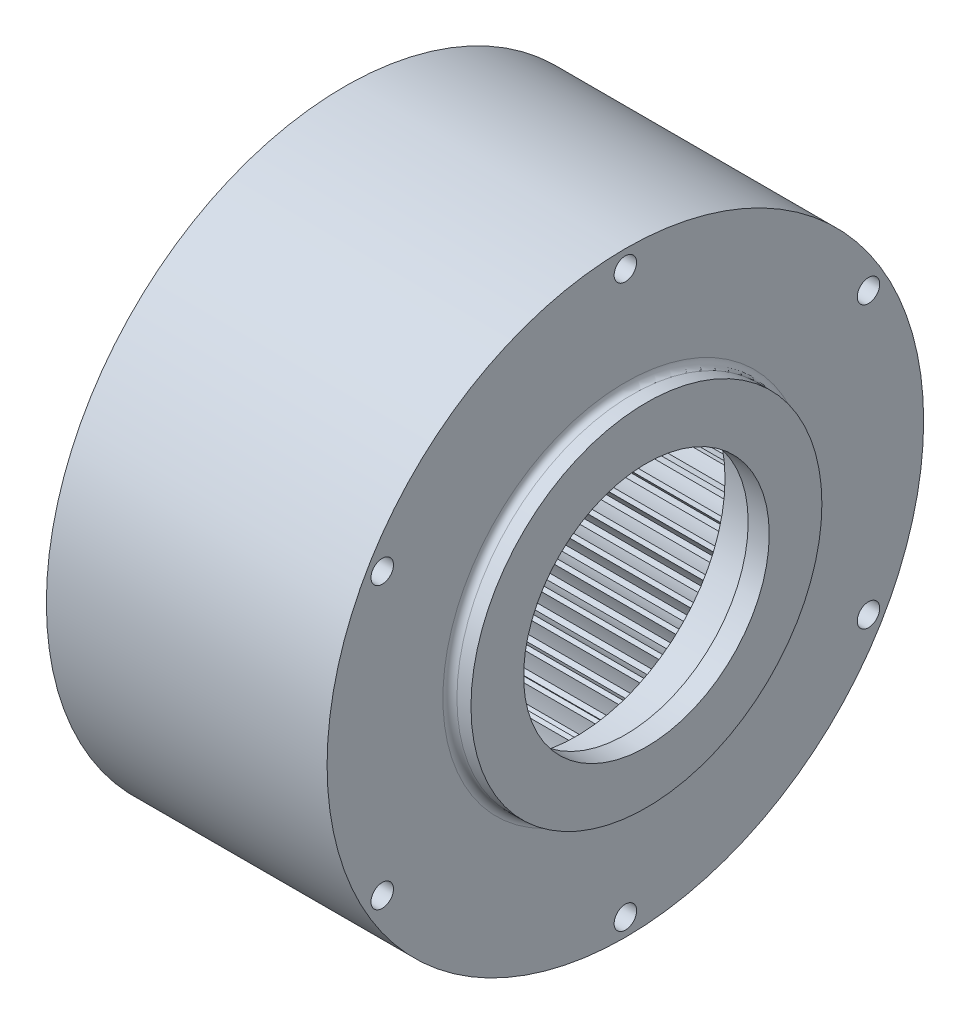
SolidWorks part; units mm, degrees
ref_plane "Plane1" through (0, 0, 0) normal (0, 0, 1) x (1, 0, 0)
ref_plane "Plane2" through (0, 0, 0) normal (0, 1, 0) x (1, 0, 0)
ref_plane "Plane3" through (0, 0, 0) normal (1, 0, 0) x (0, 0, -1)
sketch "HoldingSke" plane through (0, 0, 0) normal (0, 1, 0) x (1, 0, 0)
  line L0 (0, 0) -> (0.342, -0.9397)
  line L1 (-15, 0) -> (100, 0) construction
  line L2 (0, 0) -> (-2.1039, 2.3779)
  line L3 (0, 0) -> (-11.863, 4.5341)
  line L4 (0, 0) -> (2.9537, 8.1152)
  line L5 (0, 0) -> (-23.7986, -8.8762)
  line L6 (0, 0) -> (-10.5278, -7.1032)
  line L7 (-2.1039, 2.3779) -> (3.3635, 27.1825)
  line L8 (-76.2, 3.3779) -> (-54.61, 3.3779)
  line L9 (-71.009, 38.7566) -> (-53.1078, 45.2721)
  line L10 (-76.2, 71.12) -> (104.1128, 71.12)
  line L11 (0, 0) -> (-30, 0)
  line L12 (-76.2, 101.6) -> (-76.162, 101.6)
  line L13 (24.9733, 27.94) -> (52.9518, 28.4284)
  line L14 (24.9733, 27.94) -> (24.9743, 27.94)
  line L15 (24.9733, 27.94) -> (100.4006, 29.5858)
  circle A0 centre (0, 0) radius 42.5
  circle A1 centre (0, 0) radius 12.7
  circle A2 centre (0, 0) radius 12.7
  dimension "MHD" = 25.4
  dimension "Hub_dia" = 25.4
  dimension "Diameter" = 85
  dimension "Num_teeth" = 70
  dimension "Pitch" = 1
  dimension "Overall_len" = 25.4
  dimension "Show_teeth" = 70
  dimension "Thickness" = 12.7
  dimension "OAL" = 25.4001
  dimension "T_dim" = 21.59
  dimension "Ap" = 20
  dimension "H" = 19.05
  dimension "Pitch_radius" = 180.3128
  dimension "Width" = 30
  dimension "Backlash" = 0.038
  dimension "Addendum_fac" = 1
  dimension "Dedendum_fac" = 1.25
  dimension "Clearance_fac" = 0.25
  dimension "Dedendum_add" = 0.001
  dimension "Module" = 1
sketch "BasProSke" plane through (0, 0, 0) normal (0, 1, 0) x (1, 0, 0)
  line L0 (-10, 0) -> (60, 0) construction
  line L1 (0, 34) -> (0, 42.5)
  line L2 (0, 34) -> (30, 34)
  line L3 (30, 34) -> (30, 42.5)
  line L4 (30, 42.5) -> (0, 42.5)
  dimension "Diameter" = 85
  dimension "Thickness" = 30
  dimension "Inside_diameter" = 68
revolve "Base-Revolve" add sketch "BasProSke" angle 360 about L0
sketch "TooCutSke" plane through (0, 0, 0) normal (1, 0, 0) x (0, 0, -1)
  line L3 (0.8803, 34.9889) -> (0.8803, 53.6633) construction
  line L4 (0, 0) -> (0, 59.563) construction
  line L5 (0, 0) -> (-3.0655, 68.2587) construction
  line L6 (-15.5382, 28.9323) -> (36.4767, 31.2683) construction
  circle A0 centre (0, 0) radius 35 construction
  circle A1 centre (0, 0) radius 36.251 construction
  circle A2 centre (0, 0) radius 29.6003 construction
  circle A3 centre (0, 0) radius 33.9746 construction
  arc A4 (1.2263, 33.9525) -> (0.3588, 36.2492) centre (-15.5382, 28.9323) ccw
  arc A5 (1.2263, 33.9525) -> (-1.2263, 33.9525) centre (0, 0) ccw
  arc A6 (0.3588, 36.2492) -> (-0.3588, 36.2492) centre (0, 0) ccw
  arc A7 (-0.3588, 36.2492) -> (-1.2263, 33.9525) centre (15.5382, 28.9323) ccw
  dimension "Pitch_dia" = 70
  dimension "Base_dia" = 59.2006
  dimension "Root_dia" = 72.502
  dimension "Overcut_dia" = 67.9492
  dimension "Flank_rad" = 17.5
  dimension "Half_ang" = 2.571
  dimension "Half_CT" = 0.8803
extrude "ToothCut" cut sketch "TooCutSke" along normal through all
fillet "Breaks" [suppressed] radius 0.1
fillet "RootFillets" [suppressed] radius 0.251
pattern_circular "TeethCuts" count 70 every 5.143 about axis through (-10, 0, 0) along (1, 0, 0) of "RootFillets", "Breaks", "ToothCut"
sketch "Sketch1" plane through (30, 0, 0) normal (1, 0, 0) x (0, 0, -1)
  circle A1 centre (0, 0) radius 21.2
  circle A2 centre (0, 0) radius 42.5 construction
  circle A3 centre (0, 0) radius 42.5
extrude "Boss-Extrude1" add sketch "Sketch1" along normal blind 7
sketch "Sketch2" plane through (37, 0, 0) normal (1, 0, 0) x (0, 0, -1)
  circle A0 centre (0, 0) radius 25
  circle A1 centre (0, 0) radius 17.5
extrude "Boss-Extrude2" add sketch "Sketch2" along normal blind 3
fillet "Fillet1" radius 1 1 edges at (37, 0, -25)
sketch "Sketch4" plane through (0, 0, 0) normal (-1, 0, 0) x (0, 0, 1)
  arc A0 (-21.0165, 29.5371) -> (-21.597, 29.1154) centre (0, 0) ccw construction
  circle A1 centre (0, 0) radius 42.5
  circle A2 centre (0, 0) radius 42.5
  arc A3 (-21.597, 29.1154) -> (-20.9577, 26.7726) centre (-4.4353, 32.5399) ccw construction
  arc A4 (-20.9577, 26.7726) -> (-21.4379, 26.3897) centre (0, 0) ccw construction
  arc A5 (-21.4379, 26.3897) -> (-23.5796, 27.5343) centre (-30.7371, 11.5649) ccw construction
  arc A6 (-23.5796, 27.5343) -> (-24.1199, 27.0622) centre (0, 0) ccw construction
  arc A7 (-23.5796, 27.5343) -> (-24.1199, 27.0622) centre (0, 0) ccw construction
  arc A8 (-24.1199, 27.0622) -> (-23.2732, 24.7862) centre (-7.3343, 32.0113) ccw construction
  arc A9 (-23.2732, 24.7862) -> (-23.7171, 24.3618) centre (0, 0) ccw construction
  arc A10 (-23.7171, 24.3618) -> (-25.9528, 25.3098) centre (-31.65, 8.7631) ccw construction
  arc A11 (-25.9528, 25.3098) -> (-26.4487, 24.7912) centre (0, 0) ccw construction
  arc A12 (18.2842, -31.3021) -> (18.9002, -30.9341) centre (0, 0) ccw construction
  arc A13 (18.9002, -30.9341) -> (18.4735, -28.5435) centre (1.5006, -32.8064) ccw construction
  arc A14 (18.4735, -28.5435) -> (18.986, -28.2052) centre (0, 0) ccw construction
  arc A15 (18.986, -28.2052) -> (21.0165, -29.5371) centre (29.5767, -14.2736) ccw construction
  arc A16 (21.0165, -29.5371) -> (21.597, -29.1154) centre (0, 0) ccw construction
  arc A17 (21.0165, -29.5371) -> (21.597, -29.1154) centre (0, 0) ccw construction
  arc A18 (21.597, -29.1154) -> (20.9577, -26.7726) centre (4.4353, -32.5399) ccw construction
  arc A19 (20.9577, -26.7726) -> (21.4379, -26.3897) centre (0, 0) ccw construction
  arc A20 (21.4379, -26.3897) -> (23.5796, -27.5343) centre (30.7371, -11.5649) ccw construction
  arc A21 (23.5796, -27.5343) -> (24.1199, -27.0622) centre (0, 0) ccw construction
  arc A22 (-15.4047, 32.8151) -> (-16.0512, 32.5038) centre (0, 0) ccw construction
  arc A23 (-16.0512, 32.5038) -> (-15.8405, 30.0845) centre (1.4462, 32.8089) ccw construction
  arc A24 (-15.8405, 30.0845) -> (-16.3813, 29.7935) centre (0, 0) ccw construction
  arc A25 (-16.3813, 29.7935) -> (-18.2842, 31.3021) centre (-28.1781, 16.8674) ccw construction
  arc A26 (-18.2842, 31.3021) -> (-18.9002, 30.9341) centre (0, 0) ccw construction
  arc A27 (-18.2842, 31.3021) -> (-18.9002, 30.9341) centre (0, 0) ccw construction
  arc A28 (-18.9002, 30.9341) -> (-18.4735, 28.5435) centre (-1.5006, 32.8064) ccw construction
  arc A29 (-18.4735, 28.5435) -> (-18.986, 28.2052) centre (0, 0) ccw construction
  arc A30 (-18.986, 28.2052) -> (-21.0165, 29.5371) centre (-29.5767, 14.2736) ccw construction
  arc A31 (-21.0165, 29.5371) -> (-21.597, 29.1154) centre (0, 0) ccw construction
  arc A32 (12.4012, -34.0639) -> (13.073, -33.8117) centre (0, 0) ccw construction
  arc A33 (13.073, -33.8117) -> (13.08, -31.3833) centre (-4.3813, -32.5472) ccw construction
  arc A34 (13.08, -31.3833) -> (13.6447, -31.142) centre (0, 0) ccw construction
  arc A35 (13.6447, -31.142) -> (15.4047, -32.8151) centre (26.5527, -19.3254) ccw construction
  arc A36 (15.4047, -32.8151) -> (16.0512, -32.5038) centre (0, 0) ccw construction
  arc A37 (15.4047, -32.8151) -> (16.0512, -32.5038) centre (0, 0) ccw construction
  arc A38 (16.0512, -32.5038) -> (15.8405, -30.0845) centre (-1.4462, -32.8089) ccw construction
  arc A39 (15.8405, -30.0845) -> (16.3813, -29.7935) centre (0, 0) ccw construction
  arc A40 (16.3813, -29.7935) -> (18.2842, -31.3021) centre (28.1781, -16.8674) ccw construction
  arc A41 (18.2842, -31.3021) -> (18.9002, -30.9341) centre (0, 0) ccw construction
  arc A42 (-9.2978, 35.0384) -> (-9.9895, 34.8475) centre (0, 0) ccw construction
  arc A43 (-9.9895, 34.8475) -> (-10.2141, 32.4295) centre (7.2812, 32.0234) ccw construction
  arc A44 (-10.2141, 32.4295) -> (-10.7982, 32.2397) centre (0, 0) ccw construction
  arc A45 (-10.7982, 32.2397) -> (-12.4012, 34.0639) centre (-24.7135, 21.6277) ccw construction
  arc A46 (-12.4012, 34.0639) -> (-13.073, 33.8117) centre (0, 0) ccw construction
  arc A47 (-12.4012, 34.0639) -> (-13.073, 33.8117) centre (0, 0) ccw construction
  arc A48 (-13.073, 33.8117) -> (-13.08, 31.3833) centre (4.3813, 32.5472) ccw construction
  arc A49 (-13.08, 31.3833) -> (-13.6447, 31.142) centre (0, 0) ccw construction
  arc A50 (-13.6447, 31.142) -> (-15.4047, 32.8151) centre (-26.5527, 19.3254) ccw construction
  arc A51 (-15.4047, 32.8151) -> (-16.0512, 32.5038) centre (0, 0) ccw construction
  arc A52 (6.1195, -35.7307) -> (6.8256, -35.6026) centre (0, 0) ccw construction
  arc A53 (6.8256, -35.6026) -> (7.266, -33.2145) centre (-10.1224, -31.2418) ccw construction
  arc A54 (7.266, -33.2145) -> (7.8648, -33.0779) centre (0, 0) ccw construction
  arc A55 (7.8648, -33.0779) -> (9.2978, -35.0384) centre (22.6753, -23.756) ccw construction
  arc A56 (9.2978, -35.0384) -> (9.9895, -34.8475) centre (0, 0) ccw construction
  arc A57 (9.2978, -35.0384) -> (9.9895, -34.8475) centre (0, 0) ccw construction
  arc A58 (9.9895, -34.8475) -> (10.2141, -32.4295) centre (-7.2812, -32.0234) ccw construction
  arc A59 (10.2141, -32.4295) -> (10.7982, -32.2397) centre (0, 0) ccw construction
  arc A60 (10.7982, -32.2397) -> (12.4012, -34.0639) centre (24.7135, -21.6277) ccw construction
  arc A61 (12.4012, -34.0639) -> (13.073, -33.8117) centre (0, 0) ccw construction
  arc A62 (-2.892, 36.1355) -> (-3.6067, 36.0711) centre (0, 0) ccw construction
  arc A63 (-3.6067, 36.0711) -> (-4.2595, 33.7321) centre (12.8822, 30.2087) ccw construction
  arc A64 (-4.2595, 33.7321) -> (-4.868, 33.6497) centre (0, 0) ccw construction
  arc A65 (-4.868, 33.6497) -> (-6.1195, 35.7307) centre (-20.4545, 25.6929) ccw construction
  arc A66 (-6.1195, 35.7307) -> (-6.8256, 35.6026) centre (0, 0) ccw construction
  arc A67 (-6.1195, 35.7307) -> (-6.8256, 35.6026) centre (0, 0) ccw construction
  arc A68 (-6.8256, 35.6026) -> (-7.266, 33.2145) centre (10.1224, 31.2418) ccw construction
  arc A69 (-7.266, 33.2145) -> (-7.8648, 33.0779) centre (0, 0) ccw construction
  arc A70 (-7.8648, 33.0779) -> (-9.2978, 35.0384) centre (-22.6753, 23.756) ccw construction
  arc A71 (-9.2978, 35.0384) -> (-9.9895, 34.8475) centre (0, 0) ccw construction
  arc A72 (-0.3588, -36.2492) -> (0.3588, -36.2492) centre (0, 0) ccw construction
  arc A73 (0.3588, -36.2492) -> (1.2186, -33.9782) centre (-15.5382, -28.9323) ccw construction
  arc A74 (1.2186, -33.9782) -> (1.8321, -33.9506) centre (0, 0) ccw construction
  arc A75 (1.8321, -33.9506) -> (2.892, -36.1355) centre (18.0691, -27.423) ccw construction
  arc A76 (2.892, -36.1355) -> (3.6067, -36.0711) centre (0, 0) ccw construction
  arc A77 (2.892, -36.1355) -> (3.6067, -36.0711) centre (0, 0) ccw construction
  arc A78 (3.6067, -36.0711) -> (4.2595, -33.7321) centre (-12.8822, -30.2087) ccw construction
  arc A79 (4.2595, -33.7321) -> (4.868, -33.6497) centre (0, 0) ccw construction
  arc A80 (4.868, -33.6497) -> (6.1195, -35.7307) centre (20.4545, -25.6929) ccw construction
  arc A81 (6.1195, -35.7307) -> (6.8256, -35.6026) centre (0, 0) ccw construction
  arc A82 (3.6067, 36.0711) -> (2.892, 36.1355) centre (0, 0) ccw construction
  arc A83 (2.892, 36.1355) -> (1.8321, 33.9506) centre (18.0691, 27.423) ccw construction
  arc A84 (1.8321, 33.9506) -> (1.2186, 33.9782) centre (0, 0) ccw construction
  arc A85 (1.2186, 33.9782) -> (0.3588, 36.2492) centre (-15.5382, 28.9323) ccw construction
  arc A86 (0.3588, 36.2492) -> (-0.3588, 36.2492) centre (0, 0) ccw construction
  arc A87 (0.3588, 36.2492) -> (-0.3588, 36.2492) centre (0, 0) ccw construction
  arc A88 (-0.3588, 36.2492) -> (-1.2186, 33.9782) centre (15.5382, 28.9323) ccw construction
  arc A89 (-1.2186, 33.9782) -> (-1.8321, 33.9506) centre (0, 0) ccw construction
  arc A90 (-1.8321, 33.9506) -> (-2.892, 36.1355) centre (-18.0691, 27.423) ccw construction
  arc A91 (-2.892, 36.1355) -> (-3.6067, 36.0711) centre (0, 0) ccw construction
  arc A92 (-6.8256, -35.6026) -> (-6.1195, -35.7307) centre (0, 0) ccw construction
  arc A93 (-6.1195, -35.7307) -> (-4.868, -33.6497) centre (-20.4545, -25.6929) ccw construction
  arc A94 (-4.868, -33.6497) -> (-4.2595, -33.7321) centre (0, 0) ccw construction
  arc A95 (-4.2595, -33.7321) -> (-3.6067, -36.0711) centre (12.8822, -30.2087) ccw construction
  arc A96 (-3.6067, -36.0711) -> (-2.892, -36.1355) centre (0, 0) ccw construction
  arc A97 (-3.6067, -36.0711) -> (-2.892, -36.1355) centre (0, 0) ccw construction
  arc A98 (-2.892, -36.1355) -> (-1.8321, -33.9506) centre (-18.0691, -27.423) ccw construction
  arc A99 (-1.8321, -33.9506) -> (-1.2186, -33.9782) centre (0, 0) ccw construction
  arc A100 (-1.2186, -33.9782) -> (-0.3588, -36.2492) centre (15.5382, -28.9323) ccw construction
  arc A101 (-0.3588, -36.2492) -> (0.3588, -36.2492) centre (0, 0) ccw construction
  arc A102 (9.9895, 34.8475) -> (9.2978, 35.0384) centre (0, 0) ccw construction
  arc A103 (9.2978, 35.0384) -> (7.8648, 33.0779) centre (22.6753, 23.756) ccw construction
  arc A104 (7.8648, 33.0779) -> (7.266, 33.2145) centre (0, 0) ccw construction
  arc A105 (7.266, 33.2145) -> (6.8256, 35.6026) centre (-10.1224, 31.2418) ccw construction
  arc A106 (6.8256, 35.6026) -> (6.1195, 35.7307) centre (0, 0) ccw construction
  arc A107 (6.8256, 35.6026) -> (6.1195, 35.7307) centre (0, 0) ccw construction
  arc A108 (6.1195, 35.7307) -> (4.868, 33.6497) centre (20.4545, 25.6929) ccw construction
  arc A109 (4.868, 33.6497) -> (4.2595, 33.7321) centre (0, 0) ccw construction
  arc A110 (4.2595, 33.7321) -> (3.6067, 36.0711) centre (-12.8822, 30.2087) ccw construction
  arc A111 (3.6067, 36.0711) -> (2.892, 36.1355) centre (0, 0) ccw construction
  arc A112 (-13.073, -33.8117) -> (-12.4012, -34.0639) centre (0, 0) ccw construction
  arc A113 (-12.4012, -34.0639) -> (-10.7982, -32.2397) centre (-24.7135, -21.6277) ccw construction
  arc A114 (-10.7982, -32.2397) -> (-10.2141, -32.4295) centre (0, 0) ccw construction
  arc A115 (-10.2141, -32.4295) -> (-9.9895, -34.8475) centre (7.2812, -32.0234) ccw construction
  arc A116 (-9.9895, -34.8475) -> (-9.2978, -35.0384) centre (0, 0) ccw construction
  arc A117 (-9.9895, -34.8475) -> (-9.2978, -35.0384) centre (0, 0) ccw construction
  arc A118 (-9.2978, -35.0384) -> (-7.8648, -33.0779) centre (-22.6753, -23.756) ccw construction
  arc A119 (-7.8648, -33.0779) -> (-7.266, -33.2145) centre (0, 0) ccw construction
  arc A120 (-7.266, -33.2145) -> (-6.8256, -35.6026) centre (10.1224, -31.2418) ccw construction
  arc A121 (-6.8256, -35.6026) -> (-6.1195, -35.7307) centre (0, 0) ccw construction
  arc A122 (16.0512, 32.5038) -> (15.4047, 32.8151) centre (0, 0) ccw construction
  arc A123 (15.4047, 32.8151) -> (13.6447, 31.142) centre (26.5527, 19.3254) ccw construction
  arc A124 (13.6447, 31.142) -> (13.08, 31.3833) centre (0, 0) ccw construction
  arc A125 (13.08, 31.3833) -> (13.073, 33.8117) centre (-4.3813, 32.5472) ccw construction
  arc A126 (13.073, 33.8117) -> (12.4012, 34.0639) centre (0, 0) ccw construction
  arc A127 (13.073, 33.8117) -> (12.4012, 34.0639) centre (0, 0) ccw construction
  arc A128 (12.4012, 34.0639) -> (10.7982, 32.2397) centre (24.7135, 21.6277) ccw construction
  arc A129 (10.7982, 32.2397) -> (10.2141, 32.4295) centre (0, 0) ccw construction
  arc A130 (10.2141, 32.4295) -> (9.9895, 34.8475) centre (-7.2812, 32.0234) ccw construction
  arc A131 (9.9895, 34.8475) -> (9.2978, 35.0384) centre (0, 0) ccw construction
  arc A132 (-18.9002, -30.9341) -> (-18.2842, -31.3021) centre (0, 0) ccw construction
  arc A133 (-18.2842, -31.3021) -> (-16.3813, -29.7935) centre (-28.1781, -16.8674) ccw construction
  arc A134 (-16.3813, -29.7935) -> (-15.8405, -30.0845) centre (0, 0) ccw construction
  arc A135 (-15.8405, -30.0845) -> (-16.0512, -32.5038) centre (1.4462, -32.8089) ccw construction
  arc A136 (-16.0512, -32.5038) -> (-15.4047, -32.8151) centre (0, 0) ccw construction
  arc A137 (-16.0512, -32.5038) -> (-15.4047, -32.8151) centre (0, 0) ccw construction
  arc A138 (-15.4047, -32.8151) -> (-13.6447, -31.142) centre (-26.5527, -19.3254) ccw construction
  arc A139 (-13.6447, -31.142) -> (-13.08, -31.3833) centre (0, 0) ccw construction
  arc A140 (-13.08, -31.3833) -> (-13.073, -33.8117) centre (4.3813, -32.5472) ccw construction
  arc A141 (-13.073, -33.8117) -> (-12.4012, -34.0639) centre (0, 0) ccw construction
  arc A142 (21.597, 29.1154) -> (21.0165, 29.5371) centre (0, 0) ccw construction
  arc A143 (21.0165, 29.5371) -> (18.986, 28.2052) centre (29.5767, 14.2736) ccw construction
  arc A144 (18.986, 28.2052) -> (18.4735, 28.5435) centre (0, 0) ccw construction
  arc A145 (18.4735, 28.5435) -> (18.9002, 30.9341) centre (1.5006, 32.8064) ccw construction
  arc A146 (18.9002, 30.9341) -> (18.2842, 31.3021) centre (0, 0) ccw construction
  arc A147 (18.9002, 30.9341) -> (18.2842, 31.3021) centre (0, 0) ccw construction
  arc A148 (18.2842, 31.3021) -> (16.3813, 29.7935) centre (28.1781, 16.8674) ccw construction
  arc A149 (16.3813, 29.7935) -> (15.8405, 30.0845) centre (0, 0) ccw construction
  arc A150 (15.8405, 30.0845) -> (16.0512, 32.5038) centre (-1.4462, 32.8089) ccw construction
  arc A151 (16.0512, 32.5038) -> (15.4047, 32.8151) centre (0, 0) ccw construction
  arc A152 (-24.1199, -27.0622) -> (-23.5796, -27.5343) centre (0, 0) ccw construction
  arc A153 (-23.5796, -27.5343) -> (-21.4379, -26.3897) centre (-30.7371, -11.5649) ccw construction
  arc A154 (-21.4379, -26.3897) -> (-20.9577, -26.7726) centre (0, 0) ccw construction
  arc A155 (-20.9577, -26.7726) -> (-21.597, -29.1154) centre (-4.4353, -32.5399) ccw construction
  arc A156 (-21.597, -29.1154) -> (-21.0165, -29.5371) centre (0, 0) ccw construction
  arc A157 (-21.597, -29.1154) -> (-21.0165, -29.5371) centre (0, 0) ccw construction
  arc A158 (-21.0165, -29.5371) -> (-18.986, -28.2052) centre (-29.5767, -14.2736) ccw construction
  arc A159 (-18.986, -28.2052) -> (-18.4735, -28.5435) centre (0, 0) ccw construction
  arc A160 (-18.4735, -28.5435) -> (-18.9002, -30.9341) centre (-1.5006, -32.8064) ccw construction
  arc A161 (-18.9002, -30.9341) -> (-18.2842, -31.3021) centre (0, 0) ccw construction
  arc A162 (26.4487, 24.7912) -> (25.9528, 25.3098) centre (0, 0) ccw construction
  arc A163 (25.9528, 25.3098) -> (23.7171, 24.3618) centre (31.65, 8.7631) ccw construction
  arc A164 (23.7171, 24.3618) -> (23.2732, 24.7862) centre (0, 0) ccw construction
  arc A165 (23.2732, 24.7862) -> (24.1199, 27.0622) centre (7.3343, 32.0113) ccw construction
  arc A166 (24.1199, 27.0622) -> (23.5796, 27.5343) centre (0, 0) ccw construction
  arc A167 (24.1199, 27.0622) -> (23.5796, 27.5343) centre (0, 0) ccw construction
  arc A168 (23.5796, 27.5343) -> (21.4379, 26.3897) centre (30.7371, 11.5649) ccw construction
  arc A169 (21.4379, 26.3897) -> (20.9577, 26.7726) centre (0, 0) ccw construction
  arc A170 (20.9577, 26.7726) -> (21.597, 29.1154) centre (4.4353, 32.5399) ccw construction
  arc A171 (21.597, 29.1154) -> (21.0165, 29.5371) centre (0, 0) ccw construction
  arc A172 (-28.5645, -22.3205) -> (-28.1171, -22.8815) centre (0, 0) ccw construction
  arc A173 (-28.1171, -22.8815) -> (-25.8054, -22.1378) centre (-32.3081, -5.8908) ccw construction
  arc A174 (-25.8054, -22.1378) -> (-25.4014, -22.6002) centre (0, 0) ccw construction
  arc A175 (-25.4014, -22.6002) -> (-26.4487, -24.7912) centre (-10.1743, -31.225) ccw construction
  arc A176 (-26.4487, -24.7912) -> (-25.9528, -25.3098) centre (0, 0) ccw construction
  arc A177 (-26.4487, -24.7912) -> (-25.9528, -25.3098) centre (0, 0) ccw construction
  arc A178 (-25.9528, -25.3098) -> (-23.7171, -24.3618) centre (-31.65, -8.7631) ccw construction
  arc A179 (-23.7171, -24.3618) -> (-23.2732, -24.7862) centre (0, 0) ccw construction
  arc A180 (-23.2732, -24.7862) -> (-24.1199, -27.0622) centre (-7.3343, -32.0113) ccw construction
  arc A181 (-24.1199, -27.0622) -> (-23.5796, -27.5343) centre (0, 0) ccw construction
  arc A182 (30.4503, 19.6702) -> (30.055, 20.269) centre (0, 0) ccw construction
  arc A183 (30.055, 20.269) -> (27.6859, 19.7355) centre (32.7061, 2.971) ccw construction
  arc A184 (27.6859, 19.7355) -> (27.325, 20.2323) centre (0, 0) ccw construction
  arc A185 (27.325, 20.2323) -> (28.5645, 22.3205) centre (12.9323, 30.1873) ccw construction
  arc A186 (28.5645, 22.3205) -> (28.1171, 22.8815) centre (0, 0) ccw construction
  arc A187 (28.5645, 22.3205) -> (28.1171, 22.8815) centre (0, 0) ccw construction
  arc A188 (28.1171, 22.8815) -> (25.8054, 22.1378) centre (32.3081, 5.8908) ccw construction
  arc A189 (25.8054, 22.1378) -> (25.4014, 22.6002) centre (0, 0) ccw construction
  arc A190 (25.4014, 22.6002) -> (26.4487, 24.7912) centre (10.1743, 31.225) ccw construction
  arc A191 (26.4487, 24.7912) -> (25.9528, 25.3098) centre (0, 0) ccw construction
  arc A192 (-32.0909, -16.8614) -> (-31.7509, -17.4933) centre (0, 0) ccw construction
  arc A193 (-31.7509, -17.4933) -> (-29.3436, -17.1743) centre (-32.8407, -0.0273) ccw construction
  arc A194 (-29.3436, -17.1743) -> (-29.0286, -17.7015) centre (0, 0) ccw construction
  arc A195 (-29.0286, -17.7015) -> (-30.4503, -19.6702) centre (-15.5862, -28.9065) ccw construction
  arc A196 (-30.4503, -19.6702) -> (-30.055, -20.269) centre (0, 0) ccw construction
  arc A197 (-30.4503, -19.6702) -> (-30.055, -20.269) centre (0, 0) ccw construction
  arc A198 (-30.055, -20.269) -> (-27.6859, -19.7355) centre (-32.7061, -2.971) ccw construction
  arc A199 (-27.6859, -19.7355) -> (-27.325, -20.2323) centre (0, 0) ccw construction
  arc A200 (-27.325, -20.2323) -> (-28.5645, -22.3205) centre (-12.9323, -30.1873) ccw construction
  arc A201 (-28.5645, -22.3205) -> (-28.1171, -22.8815) centre (0, 0) ccw construction
  arc A202 (33.4732, 13.917) -> (33.1912, 14.5768) centre (0, 0) ccw construction
  arc A203 (33.1912, 14.5768) -> (30.7649, 14.4748) centre (32.711, -2.9167) ccw construction
  arc A204 (30.7649, 14.4748) -> (30.4985, 15.0281) centre (0, 0) ccw construction
  arc A205 (30.4985, 15.0281) -> (32.0909, 16.8614) centre (18.1146, 27.393) ccw construction
  arc A206 (32.0909, 16.8614) -> (31.7509, 17.4933) centre (0, 0) ccw construction
  arc A207 (32.0909, 16.8614) -> (31.7509, 17.4933) centre (0, 0) ccw construction
  arc A208 (31.7509, 17.4933) -> (29.3436, 17.1743) centre (32.8407, 0.0273) ccw construction
  arc A209 (29.3436, 17.1743) -> (29.0286, 17.7015) centre (0, 0) ccw construction
  arc A210 (29.0286, 17.7015) -> (30.4503, 19.6702) centre (15.5862, 28.9065) ccw construction
  arc A211 (30.4503, 19.6702) -> (30.055, 20.269) centre (0, 0) ccw construction
  arc A212 (-34.5859, -10.8604) -> (-34.3642, -11.5428) centre (0, 0) ccw construction
  arc A213 (-34.3642, -11.5428) -> (-31.9386, -11.6588) centre (-32.3178, 5.8371) ccw construction
  arc A214 (-31.9386, -11.6588) -> (-31.7228, -12.2337) centre (0, 0) ccw construction
  arc A215 (-31.7228, -12.2337) -> (-33.4732, -13.917) centre (-20.4972, -25.6589) ccw construction
  arc A216 (-33.4732, -13.917) -> (-33.1912, -14.5768) centre (0, 0) ccw construction
  arc A217 (-33.4732, -13.917) -> (-33.1912, -14.5768) centre (0, 0) ccw construction
  arc A218 (-33.1912, -14.5768) -> (-30.7649, -14.4748) centre (-32.711, 2.9167) ccw construction
  arc A219 (-30.7649, -14.4748) -> (-30.4985, -15.0281) centre (0, 0) ccw construction
  arc A220 (-30.4985, -15.0281) -> (-32.0909, -16.8614) centre (-18.1146, -27.393) ccw construction
  arc A221 (-32.0909, -16.8614) -> (-31.7509, -17.4933) centre (0, 0) ccw construction
  arc A222 (35.4202, 7.7164) -> (35.2605, 8.416) centre (0, 0) ccw construction
  arc A223 (35.2605, 8.416) -> (32.8551, 8.7489) centre (31.6645, -8.7106) ccw construction
  arc A224 (32.8551, 8.7489) -> (32.6917, 9.3409) centre (0, 0) ccw construction
  arc A225 (32.6917, 9.3409) -> (34.5859, 10.8604) centre (22.7147, 23.7183) ccw construction
  arc A226 (34.5859, 10.8604) -> (34.3642, 11.5428) centre (0, 0) ccw construction
  arc A227 (34.5859, 10.8604) -> (34.3642, 11.5428) centre (0, 0) ccw construction
  arc A228 (34.3642, 11.5428) -> (31.9386, 11.6588) centre (32.3178, -5.8371) ccw construction
  arc A229 (31.9386, 11.6588) -> (31.7228, 12.2337) centre (0, 0) ccw construction
  arc A230 (31.7228, 12.2337) -> (33.4732, 13.917) centre (20.4972, 25.6589) ccw construction
  arc A231 (33.4732, 13.917) -> (33.1912, 14.5768) centre (0, 0) ccw construction
  arc A232 (-35.9693, -4.5103) -> (-35.873, -5.2214) centre (0, 0) ccw construction
  arc A233 (-35.873, -5.2214) -> (-33.5071, -5.7686) centre (-30.7562, 11.5139) ccw construction
  arc A234 (-33.5071, -5.7686) -> (-33.3974, -6.3728) centre (0, 0) ccw construction
  arc A235 (-33.3974, -6.3728) -> (-35.4202, -7.7164) centre (-24.7494, -21.5867) ccw construction
  arc A236 (-35.4202, -7.7164) -> (-35.2605, -8.416) centre (0, 0) ccw construction
  arc A237 (-35.4202, -7.7164) -> (-35.2605, -8.416) centre (0, 0) ccw construction
  arc A238 (-35.2605, -8.416) -> (-32.8551, -8.7489) centre (-31.6645, 8.7106) ccw construction
  arc A239 (-32.8551, -8.7489) -> (-32.6917, -9.3409) centre (0, 0) ccw construction
  arc A240 (-32.6917, -9.3409) -> (-34.5859, -10.8604) centre (-22.7147, -23.7183) ccw construction
  arc A241 (-34.5859, -10.8604) -> (-34.3642, -11.5428) centre (0, 0) ccw construction
  arc A242 (36.2288, 1.2679) -> (36.1966, 1.9847) centre (0, 0) ccw construction
  arc A243 (36.1966, 1.9847) -> (33.8893, 2.7418) centre (29.6003, -14.2245) ccw construction
  arc A244 (33.8893, 2.7418) -> (33.8342, 3.3534) centre (0, 0) ccw construction
  arc A245 (33.8342, 3.3534) -> (35.9693, 4.5103) centre (26.5847, 19.2812) ccw construction
  arc A246 (35.9693, 4.5103) -> (35.873, 5.2214) centre (0, 0) ccw construction
  arc A247 (35.9693, 4.5103) -> (35.873, 5.2214) centre (0, 0) ccw construction
  arc A248 (35.873, 5.2214) -> (33.5071, 5.7686) centre (30.7562, -11.5139) ccw construction
  arc A249 (33.5071, 5.7686) -> (33.3974, 6.3728) centre (0, 0) ccw construction
  arc A250 (33.3974, 6.3728) -> (35.4202, 7.7164) centre (24.7494, 21.5867) ccw construction
  arc A251 (35.4202, 7.7164) -> (35.2605, 8.416) centre (0, 0) ccw construction
  arc A252 (-36.1966, 1.9847) -> (-36.2288, 1.2679) centre (0, 0) ccw construction
  arc A253 (-36.2288, 1.2679) -> (-33.9986, 0.3071) centre (-28.2061, 16.8206) ccw construction
  arc A254 (-33.9986, 0.3071) -> (-33.9986, -0.3071) centre (0, 0) ccw construction
  arc A255 (-33.9986, -0.3071) -> (-36.2288, -1.2679) centre (-28.2061, -16.8206) ccw construction
  arc A256 (-36.2288, -1.2679) -> (-36.1966, -1.9847) centre (0, 0) ccw construction
  arc A257 (-36.2288, -1.2679) -> (-36.1966, -1.9847) centre (0, 0) ccw construction
  arc A258 (-36.1966, -1.9847) -> (-33.8893, -2.7418) centre (-29.6003, 14.2245) ccw construction
  arc A259 (-33.8893, -2.7418) -> (-33.8342, -3.3534) centre (0, 0) ccw construction
  arc A260 (-33.8342, -3.3534) -> (-35.9693, -4.5103) centre (-26.5847, -19.2812) ccw construction
  arc A261 (-35.9693, -4.5103) -> (-35.873, -5.2214) centre (0, 0) ccw construction
  arc A262 (35.873, -5.2214) -> (35.9693, -4.5103) centre (0, 0) ccw construction
  arc A263 (35.9693, -4.5103) -> (33.8342, -3.3534) centre (26.5847, -19.2812) ccw construction
  arc A264 (33.8342, -3.3534) -> (33.8893, -2.7418) centre (0, 0) ccw construction
  arc A265 (33.8893, -2.7418) -> (36.1966, -1.9847) centre (29.6003, 14.2245) ccw construction
  arc A266 (36.1966, -1.9847) -> (36.2288, -1.2679) centre (0, 0) ccw construction
  arc A267 (36.1966, -1.9847) -> (36.2288, -1.2679) centre (0, 0) ccw construction
  arc A268 (36.2288, -1.2679) -> (33.9986, -0.3071) centre (28.2061, -16.8206) ccw construction
  arc A269 (33.9986, -0.3071) -> (33.9986, 0.3071) centre (0, 0) ccw construction
  arc A270 (33.9986, 0.3071) -> (36.2288, 1.2679) centre (28.2061, 16.8206) ccw construction
  arc A271 (36.2288, 1.2679) -> (36.1966, 1.9847) centre (0, 0) ccw construction
  arc A272 (-35.2605, 8.416) -> (-35.4202, 7.7164) centre (0, 0) ccw construction
  arc A273 (-35.4202, 7.7164) -> (-33.3974, 6.3728) centre (-24.7494, 21.5867) ccw construction
  arc A274 (-33.3974, 6.3728) -> (-33.5071, 5.7686) centre (0, 0) ccw construction
  arc A275 (-33.5071, 5.7686) -> (-35.873, 5.2214) centre (-30.7562, -11.5139) ccw construction
  arc A276 (-35.873, 5.2214) -> (-35.9693, 4.5103) centre (0, 0) ccw construction
  arc A277 (-35.873, 5.2214) -> (-35.9693, 4.5103) centre (0, 0) ccw construction
  arc A278 (-35.9693, 4.5103) -> (-33.8342, 3.3534) centre (-26.5847, 19.2812) ccw construction
  arc A279 (-33.8342, 3.3534) -> (-33.8893, 2.7418) centre (0, 0) ccw construction
  arc A280 (-33.8893, 2.7418) -> (-36.1966, 1.9847) centre (-29.6003, -14.2245) ccw construction
  arc A281 (-36.1966, 1.9847) -> (-36.2288, 1.2679) centre (0, 0) ccw construction
  arc A282 (34.3642, -11.5428) -> (34.5859, -10.8604) centre (0, 0) ccw construction
  arc A283 (34.5859, -10.8604) -> (32.6917, -9.3409) centre (22.7147, -23.7183) ccw construction
  arc A284 (32.6917, -9.3409) -> (32.8551, -8.7489) centre (0, 0) ccw construction
  arc A285 (32.8551, -8.7489) -> (35.2605, -8.416) centre (31.6645, 8.7106) ccw construction
  arc A286 (35.2605, -8.416) -> (35.4202, -7.7164) centre (0, 0) ccw construction
  arc A287 (35.2605, -8.416) -> (35.4202, -7.7164) centre (0, 0) ccw construction
  arc A288 (35.4202, -7.7164) -> (33.3974, -6.3728) centre (24.7494, -21.5867) ccw construction
  arc A289 (33.3974, -6.3728) -> (33.5071, -5.7686) centre (0, 0) ccw construction
  arc A290 (33.5071, -5.7686) -> (35.873, -5.2214) centre (30.7562, 11.5139) ccw construction
  arc A291 (35.873, -5.2214) -> (35.9693, -4.5103) centre (0, 0) ccw construction
  arc A292 (-33.1912, 14.5768) -> (-33.4732, 13.917) centre (0, 0) ccw construction
  arc A293 (-33.4732, 13.917) -> (-31.7228, 12.2337) centre (-20.4972, 25.6589) ccw construction
  arc A294 (-31.7228, 12.2337) -> (-31.9386, 11.6588) centre (0, 0) ccw construction
  arc A295 (-31.9386, 11.6588) -> (-34.3642, 11.5428) centre (-32.3178, -5.8371) ccw construction
  arc A296 (-34.3642, 11.5428) -> (-34.5859, 10.8604) centre (0, 0) ccw construction
  arc A297 (-34.3642, 11.5428) -> (-34.5859, 10.8604) centre (0, 0) ccw construction
  arc A298 (-34.5859, 10.8604) -> (-32.6917, 9.3409) centre (-22.7147, 23.7183) ccw construction
  arc A299 (-32.6917, 9.3409) -> (-32.8551, 8.7489) centre (0, 0) ccw construction
  arc A300 (-32.8551, 8.7489) -> (-35.2605, 8.416) centre (-31.6645, -8.7106) ccw construction
  arc A301 (-35.2605, 8.416) -> (-35.4202, 7.7164) centre (0, 0) ccw construction
  arc A302 (31.7509, -17.4933) -> (32.0909, -16.8614) centre (0, 0) ccw construction
  arc A303 (32.0909, -16.8614) -> (30.4985, -15.0281) centre (18.1146, -27.393) ccw construction
  arc A304 (30.4985, -15.0281) -> (30.7649, -14.4748) centre (0, 0) ccw construction
  arc A305 (30.7649, -14.4748) -> (33.1912, -14.5768) centre (32.711, 2.9167) ccw construction
  arc A306 (33.1912, -14.5768) -> (33.4732, -13.917) centre (0, 0) ccw construction
  arc A307 (33.1912, -14.5768) -> (33.4732, -13.917) centre (0, 0) ccw construction
  arc A308 (33.4732, -13.917) -> (31.7228, -12.2337) centre (20.4972, -25.6589) ccw construction
  arc A309 (31.7228, -12.2337) -> (31.9386, -11.6588) centre (0, 0) ccw construction
  arc A310 (31.9386, -11.6588) -> (34.3642, -11.5428) centre (32.3178, 5.8371) ccw construction
  arc A311 (34.3642, -11.5428) -> (34.5859, -10.8604) centre (0, 0) ccw construction
  arc A312 (-30.055, 20.269) -> (-30.4503, 19.6702) centre (0, 0) ccw construction
  arc A313 (-30.4503, 19.6702) -> (-29.0286, 17.7015) centre (-15.5862, 28.9065) ccw construction
  arc A314 (-29.0286, 17.7015) -> (-29.3436, 17.1743) centre (0, 0) ccw construction
  arc A315 (-29.3436, 17.1743) -> (-31.7509, 17.4933) centre (-32.8407, 0.0273) ccw construction
  arc A316 (-31.7509, 17.4933) -> (-32.0909, 16.8614) centre (0, 0) ccw construction
  arc A317 (-31.7509, 17.4933) -> (-32.0909, 16.8614) centre (0, 0) ccw construction
  arc A318 (-32.0909, 16.8614) -> (-30.4985, 15.0281) centre (-18.1146, 27.393) ccw construction
  arc A319 (-30.4985, 15.0281) -> (-30.7649, 14.4748) centre (0, 0) ccw construction
  arc A320 (-30.7649, 14.4748) -> (-33.1912, 14.5768) centre (-32.711, -2.9167) ccw construction
  arc A321 (-33.1912, 14.5768) -> (-33.4732, 13.917) centre (0, 0) ccw construction
  arc A322 (28.1171, -22.8815) -> (28.5645, -22.3205) centre (0, 0) ccw construction
  arc A323 (28.5645, -22.3205) -> (27.325, -20.2323) centre (12.9323, -30.1873) ccw construction
  arc A324 (27.325, -20.2323) -> (27.6859, -19.7355) centre (0, 0) ccw construction
  arc A325 (27.6859, -19.7355) -> (30.055, -20.269) centre (32.7061, -2.971) ccw construction
  arc A326 (30.055, -20.269) -> (30.4503, -19.6702) centre (0, 0) ccw construction
  arc A327 (30.055, -20.269) -> (30.4503, -19.6702) centre (0, 0) ccw construction
  arc A328 (30.4503, -19.6702) -> (29.0286, -17.7015) centre (15.5862, -28.9065) ccw construction
  arc A329 (29.0286, -17.7015) -> (29.3436, -17.1743) centre (0, 0) ccw construction
  arc A330 (29.3436, -17.1743) -> (31.7509, -17.4933) centre (32.8407, -0.0273) ccw construction
  arc A331 (31.7509, -17.4933) -> (32.0909, -16.8614) centre (0, 0) ccw construction
  arc A332 (-25.9528, 25.3098) -> (-26.4487, 24.7912) centre (0, 0) ccw construction
  arc A333 (-26.4487, 24.7912) -> (-25.4014, 22.6002) centre (-10.1743, 31.225) ccw construction
  arc A334 (-25.4014, 22.6002) -> (-25.8054, 22.1378) centre (0, 0) ccw construction
  arc A335 (-25.8054, 22.1378) -> (-28.1171, 22.8815) centre (-32.3081, 5.8908) ccw construction
  arc A336 (-28.1171, 22.8815) -> (-28.5645, 22.3205) centre (0, 0) ccw construction
  arc A337 (-28.1171, 22.8815) -> (-28.5645, 22.3205) centre (0, 0) ccw construction
  arc A338 (-28.5645, 22.3205) -> (-27.325, 20.2323) centre (-12.9323, 30.1873) ccw construction
  arc A339 (-27.325, 20.2323) -> (-27.6859, 19.7355) centre (0, 0) ccw construction
  arc A340 (-27.6859, 19.7355) -> (-30.055, 20.269) centre (-32.7061, 2.971) ccw construction
  arc A341 (-30.055, 20.269) -> (-30.4503, 19.6702) centre (0, 0) ccw construction
  arc A342 (23.5796, -27.5343) -> (24.1199, -27.0622) centre (0, 0) ccw construction
  arc A343 (24.1199, -27.0622) -> (23.2732, -24.7862) centre (7.3343, -32.0113) ccw construction
  arc A344 (23.2732, -24.7862) -> (23.7171, -24.3618) centre (0, 0) ccw construction
  arc A345 (23.7171, -24.3618) -> (25.9528, -25.3098) centre (31.65, -8.7631) ccw construction
  arc A346 (25.9528, -25.3098) -> (26.4487, -24.7912) centre (0, 0) ccw construction
  arc A347 (25.9528, -25.3098) -> (26.4487, -24.7912) centre (0, 0) ccw construction
  arc A348 (26.4487, -24.7912) -> (25.4014, -22.6002) centre (10.1743, -31.225) ccw construction
  arc A349 (25.4014, -22.6002) -> (25.8054, -22.1378) centre (0, 0) ccw construction
  arc A350 (25.8054, -22.1378) -> (28.1171, -22.8815) centre (32.3081, -5.8908) ccw construction
  arc A351 (28.1171, -22.8815) -> (28.5645, -22.3205) centre (0, 0) ccw construction
  arc A352 (-21.0165, 29.5371) -> (-21.597, 29.1154) centre (0, 0) ccw
  arc A353 (-21.597, 29.1154) -> (-20.9577, 26.7726) centre (-4.4353, 32.5399) ccw
  arc A354 (-20.9577, 26.7726) -> (-21.4379, 26.3897) centre (0, 0) ccw
  arc A355 (-21.4379, 26.3897) -> (-23.5796, 27.5343) centre (-30.7371, 11.5649) ccw
  arc A356 (-23.5796, 27.5343) -> (-24.1199, 27.0622) centre (0, 0) ccw
  arc A357 (-23.5796, 27.5343) -> (-24.1199, 27.0622) centre (0, 0) ccw
  arc A358 (-24.1199, 27.0622) -> (-23.2732, 24.7862) centre (-7.3343, 32.0113) ccw
  arc A359 (-23.2732, 24.7862) -> (-23.7171, 24.3618) centre (0, 0) ccw
  arc A360 (-23.7171, 24.3618) -> (-25.9528, 25.3098) centre (-31.65, 8.7631) ccw
  arc A361 (-25.9528, 25.3098) -> (-26.4487, 24.7912) centre (0, 0) ccw
  arc A362 (18.2842, -31.3021) -> (18.9002, -30.9341) centre (0, 0) ccw
  arc A363 (18.9002, -30.9341) -> (18.4735, -28.5435) centre (1.5006, -32.8064) ccw
  arc A364 (18.4735, -28.5435) -> (18.986, -28.2052) centre (0, 0) ccw
  arc A365 (18.986, -28.2052) -> (21.0165, -29.5371) centre (29.5767, -14.2736) ccw
  arc A366 (21.0165, -29.5371) -> (21.597, -29.1154) centre (0, 0) ccw
  arc A367 (21.0165, -29.5371) -> (21.597, -29.1154) centre (0, 0) ccw
  arc A368 (21.597, -29.1154) -> (20.9577, -26.7726) centre (4.4353, -32.5399) ccw
  arc A369 (20.9577, -26.7726) -> (21.4379, -26.3897) centre (0, 0) ccw
  arc A370 (21.4379, -26.3897) -> (23.5796, -27.5343) centre (30.7371, -11.5649) ccw
  arc A371 (23.5796, -27.5343) -> (24.1199, -27.0622) centre (0, 0) ccw
  arc A372 (-15.4047, 32.8151) -> (-16.0512, 32.5038) centre (0, 0) ccw
  arc A373 (-16.0512, 32.5038) -> (-15.8405, 30.0845) centre (1.4462, 32.8089) ccw
  arc A374 (-15.8405, 30.0845) -> (-16.3813, 29.7935) centre (0, 0) ccw
  arc A375 (-16.3813, 29.7935) -> (-18.2842, 31.3021) centre (-28.1781, 16.8674) ccw
  arc A376 (-18.2842, 31.3021) -> (-18.9002, 30.9341) centre (0, 0) ccw
  arc A377 (-18.2842, 31.3021) -> (-18.9002, 30.9341) centre (0, 0) ccw
  arc A378 (-18.9002, 30.9341) -> (-18.4735, 28.5435) centre (-1.5006, 32.8064) ccw
  arc A379 (-18.4735, 28.5435) -> (-18.986, 28.2052) centre (0, 0) ccw
  arc A380 (-18.986, 28.2052) -> (-21.0165, 29.5371) centre (-29.5767, 14.2736) ccw
  arc A381 (-21.0165, 29.5371) -> (-21.597, 29.1154) centre (0, 0) ccw
  arc A382 (12.4012, -34.0639) -> (13.073, -33.8117) centre (0, 0) ccw
  arc A383 (13.073, -33.8117) -> (13.08, -31.3833) centre (-4.3813, -32.5472) ccw
  arc A384 (13.08, -31.3833) -> (13.6447, -31.142) centre (0, 0) ccw
  arc A385 (13.6447, -31.142) -> (15.4047, -32.8151) centre (26.5527, -19.3254) ccw
  arc A386 (15.4047, -32.8151) -> (16.0512, -32.5038) centre (0, 0) ccw
  arc A387 (15.4047, -32.8151) -> (16.0512, -32.5038) centre (0, 0) ccw
  arc A388 (16.0512, -32.5038) -> (15.8405, -30.0845) centre (-1.4462, -32.8089) ccw
  arc A389 (15.8405, -30.0845) -> (16.3813, -29.7935) centre (0, 0) ccw
  arc A390 (16.3813, -29.7935) -> (18.2842, -31.3021) centre (28.1781, -16.8674) ccw
  arc A391 (18.2842, -31.3021) -> (18.9002, -30.9341) centre (0, 0) ccw
  arc A392 (-9.2978, 35.0384) -> (-9.9895, 34.8475) centre (0, 0) ccw
  arc A393 (-9.9895, 34.8475) -> (-10.2141, 32.4295) centre (7.2812, 32.0234) ccw
  arc A394 (-10.2141, 32.4295) -> (-10.7982, 32.2397) centre (0, 0) ccw
  arc A395 (-10.7982, 32.2397) -> (-12.4012, 34.0639) centre (-24.7135, 21.6277) ccw
  arc A396 (-12.4012, 34.0639) -> (-13.073, 33.8117) centre (0, 0) ccw
  arc A397 (-12.4012, 34.0639) -> (-13.073, 33.8117) centre (0, 0) ccw
  arc A398 (-13.073, 33.8117) -> (-13.08, 31.3833) centre (4.3813, 32.5472) ccw
  arc A399 (-13.08, 31.3833) -> (-13.6447, 31.142) centre (0, 0) ccw
  arc A400 (-13.6447, 31.142) -> (-15.4047, 32.8151) centre (-26.5527, 19.3254) ccw
  arc A401 (-15.4047, 32.8151) -> (-16.0512, 32.5038) centre (0, 0) ccw
  arc A402 (6.1195, -35.7307) -> (6.8256, -35.6026) centre (0, 0) ccw
  arc A403 (6.8256, -35.6026) -> (7.266, -33.2145) centre (-10.1224, -31.2418) ccw
  arc A404 (7.266, -33.2145) -> (7.8648, -33.0779) centre (0, 0) ccw
  arc A405 (7.8648, -33.0779) -> (9.2978, -35.0384) centre (22.6753, -23.756) ccw
  arc A406 (9.2978, -35.0384) -> (9.9895, -34.8475) centre (0, 0) ccw
  arc A407 (9.2978, -35.0384) -> (9.9895, -34.8475) centre (0, 0) ccw
  arc A408 (9.9895, -34.8475) -> (10.2141, -32.4295) centre (-7.2812, -32.0234) ccw
  arc A409 (10.2141, -32.4295) -> (10.7982, -32.2397) centre (0, 0) ccw
  arc A410 (10.7982, -32.2397) -> (12.4012, -34.0639) centre (24.7135, -21.6277) ccw
  arc A411 (12.4012, -34.0639) -> (13.073, -33.8117) centre (0, 0) ccw
  arc A412 (-2.892, 36.1355) -> (-3.6067, 36.0711) centre (0, 0) ccw
  arc A413 (-3.6067, 36.0711) -> (-4.2595, 33.7321) centre (12.8822, 30.2087) ccw
  arc A414 (-4.2595, 33.7321) -> (-4.868, 33.6497) centre (0, 0) ccw
  arc A415 (-4.868, 33.6497) -> (-6.1195, 35.7307) centre (-20.4545, 25.6929) ccw
  arc A416 (-6.1195, 35.7307) -> (-6.8256, 35.6026) centre (0, 0) ccw
  arc A417 (-6.1195, 35.7307) -> (-6.8256, 35.6026) centre (0, 0) ccw
  arc A418 (-6.8256, 35.6026) -> (-7.266, 33.2145) centre (10.1224, 31.2418) ccw
  arc A419 (-7.266, 33.2145) -> (-7.8648, 33.0779) centre (0, 0) ccw
  arc A420 (-7.8648, 33.0779) -> (-9.2978, 35.0384) centre (-22.6753, 23.756) ccw
  arc A421 (-9.2978, 35.0384) -> (-9.9895, 34.8475) centre (0, 0) ccw
  arc A422 (-0.3588, -36.2492) -> (0.3588, -36.2492) centre (0, 0) ccw
  arc A423 (0.3588, -36.2492) -> (1.2186, -33.9782) centre (-15.5382, -28.9323) ccw
  arc A424 (1.2186, -33.9782) -> (1.8321, -33.9506) centre (0, 0) ccw
  arc A425 (1.8321, -33.9506) -> (2.892, -36.1355) centre (18.0691, -27.423) ccw
  arc A426 (2.892, -36.1355) -> (3.6067, -36.0711) centre (0, 0) ccw
  arc A427 (2.892, -36.1355) -> (3.6067, -36.0711) centre (0, 0) ccw
  arc A428 (3.6067, -36.0711) -> (4.2595, -33.7321) centre (-12.8822, -30.2087) ccw
  arc A429 (4.2595, -33.7321) -> (4.868, -33.6497) centre (0, 0) ccw
  arc A430 (4.868, -33.6497) -> (6.1195, -35.7307) centre (20.4545, -25.6929) ccw
  arc A431 (6.1195, -35.7307) -> (6.8256, -35.6026) centre (0, 0) ccw
  arc A432 (3.6067, 36.0711) -> (2.892, 36.1355) centre (0, 0) ccw
  arc A433 (2.892, 36.1355) -> (1.8321, 33.9506) centre (18.0691, 27.423) ccw
  arc A434 (1.8321, 33.9506) -> (1.2186, 33.9782) centre (0, 0) ccw
  arc A435 (1.2186, 33.9782) -> (0.3588, 36.2492) centre (-15.5382, 28.9323) ccw
  arc A436 (0.3588, 36.2492) -> (-0.3588, 36.2492) centre (0, 0) ccw
  arc A437 (0.3588, 36.2492) -> (-0.3588, 36.2492) centre (0, 0) ccw
  arc A438 (-0.3588, 36.2492) -> (-1.2186, 33.9782) centre (15.5382, 28.9323) ccw
  arc A439 (-1.2186, 33.9782) -> (-1.8321, 33.9506) centre (0, 0) ccw
  arc A440 (-1.8321, 33.9506) -> (-2.892, 36.1355) centre (-18.0691, 27.423) ccw
  arc A441 (-2.892, 36.1355) -> (-3.6067, 36.0711) centre (0, 0) ccw
  arc A442 (-6.8256, -35.6026) -> (-6.1195, -35.7307) centre (0, 0) ccw
  arc A443 (-6.1195, -35.7307) -> (-4.868, -33.6497) centre (-20.4545, -25.6929) ccw
  arc A444 (-4.868, -33.6497) -> (-4.2595, -33.7321) centre (0, 0) ccw
  arc A445 (-4.2595, -33.7321) -> (-3.6067, -36.0711) centre (12.8822, -30.2087) ccw
  arc A446 (-3.6067, -36.0711) -> (-2.892, -36.1355) centre (0, 0) ccw
  arc A447 (-3.6067, -36.0711) -> (-2.892, -36.1355) centre (0, 0) ccw
  arc A448 (-2.892, -36.1355) -> (-1.8321, -33.9506) centre (-18.0691, -27.423) ccw
  arc A449 (-1.8321, -33.9506) -> (-1.2186, -33.9782) centre (0, 0) ccw
  arc A450 (-1.2186, -33.9782) -> (-0.3588, -36.2492) centre (15.5382, -28.9323) ccw
  arc A451 (-0.3588, -36.2492) -> (0.3588, -36.2492) centre (0, 0) ccw
  arc A452 (9.9895, 34.8475) -> (9.2978, 35.0384) centre (0, 0) ccw
  arc A453 (9.2978, 35.0384) -> (7.8648, 33.0779) centre (22.6753, 23.756) ccw
  arc A454 (7.8648, 33.0779) -> (7.266, 33.2145) centre (0, 0) ccw
  arc A455 (7.266, 33.2145) -> (6.8256, 35.6026) centre (-10.1224, 31.2418) ccw
  arc A456 (6.8256, 35.6026) -> (6.1195, 35.7307) centre (0, 0) ccw
  arc A457 (6.8256, 35.6026) -> (6.1195, 35.7307) centre (0, 0) ccw
  arc A458 (6.1195, 35.7307) -> (4.868, 33.6497) centre (20.4545, 25.6929) ccw
  arc A459 (4.868, 33.6497) -> (4.2595, 33.7321) centre (0, 0) ccw
  arc A460 (4.2595, 33.7321) -> (3.6067, 36.0711) centre (-12.8822, 30.2087) ccw
  arc A461 (3.6067, 36.0711) -> (2.892, 36.1355) centre (0, 0) ccw
  arc A462 (-13.073, -33.8117) -> (-12.4012, -34.0639) centre (0, 0) ccw
  arc A463 (-12.4012, -34.0639) -> (-10.7982, -32.2397) centre (-24.7135, -21.6277) ccw
  arc A464 (-10.7982, -32.2397) -> (-10.2141, -32.4295) centre (0, 0) ccw
  arc A465 (-10.2141, -32.4295) -> (-9.9895, -34.8475) centre (7.2812, -32.0234) ccw
  arc A466 (-9.9895, -34.8475) -> (-9.2978, -35.0384) centre (0, 0) ccw
  arc A467 (-9.9895, -34.8475) -> (-9.2978, -35.0384) centre (0, 0) ccw
  arc A468 (-9.2978, -35.0384) -> (-7.8648, -33.0779) centre (-22.6753, -23.756) ccw
  arc A469 (-7.8648, -33.0779) -> (-7.266, -33.2145) centre (0, 0) ccw
  arc A470 (-7.266, -33.2145) -> (-6.8256, -35.6026) centre (10.1224, -31.2418) ccw
  arc A471 (-6.8256, -35.6026) -> (-6.1195, -35.7307) centre (0, 0) ccw
  arc A472 (16.0512, 32.5038) -> (15.4047, 32.8151) centre (0, 0) ccw
  arc A473 (15.4047, 32.8151) -> (13.6447, 31.142) centre (26.5527, 19.3254) ccw
  arc A474 (13.6447, 31.142) -> (13.08, 31.3833) centre (0, 0) ccw
  arc A475 (13.08, 31.3833) -> (13.073, 33.8117) centre (-4.3813, 32.5472) ccw
  arc A476 (13.073, 33.8117) -> (12.4012, 34.0639) centre (0, 0) ccw
  arc A477 (13.073, 33.8117) -> (12.4012, 34.0639) centre (0, 0) ccw
  arc A478 (12.4012, 34.0639) -> (10.7982, 32.2397) centre (24.7135, 21.6277) ccw
  arc A479 (10.7982, 32.2397) -> (10.2141, 32.4295) centre (0, 0) ccw
  arc A480 (10.2141, 32.4295) -> (9.9895, 34.8475) centre (-7.2812, 32.0234) ccw
  arc A481 (9.9895, 34.8475) -> (9.2978, 35.0384) centre (0, 0) ccw
  arc A482 (-18.9002, -30.9341) -> (-18.2842, -31.3021) centre (0, 0) ccw
  arc A483 (-18.2842, -31.3021) -> (-16.3813, -29.7935) centre (-28.1781, -16.8674) ccw
  arc A484 (-16.3813, -29.7935) -> (-15.8405, -30.0845) centre (0, 0) ccw
  arc A485 (-15.8405, -30.0845) -> (-16.0512, -32.5038) centre (1.4462, -32.8089) ccw
  arc A486 (-16.0512, -32.5038) -> (-15.4047, -32.8151) centre (0, 0) ccw
  arc A487 (-16.0512, -32.5038) -> (-15.4047, -32.8151) centre (0, 0) ccw
  arc A488 (-15.4047, -32.8151) -> (-13.6447, -31.142) centre (-26.5527, -19.3254) ccw
  arc A489 (-13.6447, -31.142) -> (-13.08, -31.3833) centre (0, 0) ccw
  arc A490 (-13.08, -31.3833) -> (-13.073, -33.8117) centre (4.3813, -32.5472) ccw
  arc A491 (-13.073, -33.8117) -> (-12.4012, -34.0639) centre (0, 0) ccw
  arc A492 (21.597, 29.1154) -> (21.0165, 29.5371) centre (0, 0) ccw
  arc A493 (21.0165, 29.5371) -> (18.986, 28.2052) centre (29.5767, 14.2736) ccw
  arc A494 (18.986, 28.2052) -> (18.4735, 28.5435) centre (0, 0) ccw
  arc A495 (18.4735, 28.5435) -> (18.9002, 30.9341) centre (1.5006, 32.8064) ccw
  arc A496 (18.9002, 30.9341) -> (18.2842, 31.3021) centre (0, 0) ccw
  arc A497 (18.9002, 30.9341) -> (18.2842, 31.3021) centre (0, 0) ccw
  arc A498 (18.2842, 31.3021) -> (16.3813, 29.7935) centre (28.1781, 16.8674) ccw
  arc A499 (16.3813, 29.7935) -> (15.8405, 30.0845) centre (0, 0) ccw
  arc A500 (15.8405, 30.0845) -> (16.0512, 32.5038) centre (-1.4462, 32.8089) ccw
  arc A501 (16.0512, 32.5038) -> (15.4047, 32.8151) centre (0, 0) ccw
  arc A502 (-24.1199, -27.0622) -> (-23.5796, -27.5343) centre (0, 0) ccw
  arc A503 (-23.5796, -27.5343) -> (-21.4379, -26.3897) centre (-30.7371, -11.5649) ccw
  arc A504 (-21.4379, -26.3897) -> (-20.9577, -26.7726) centre (0, 0) ccw
  arc A505 (-20.9577, -26.7726) -> (-21.597, -29.1154) centre (-4.4353, -32.5399) ccw
  arc A506 (-21.597, -29.1154) -> (-21.0165, -29.5371) centre (0, 0) ccw
  arc A507 (-21.597, -29.1154) -> (-21.0165, -29.5371) centre (0, 0) ccw
  arc A508 (-21.0165, -29.5371) -> (-18.986, -28.2052) centre (-29.5767, -14.2736) ccw
  arc A509 (-18.986, -28.2052) -> (-18.4735, -28.5435) centre (0, 0) ccw
  arc A510 (-18.4735, -28.5435) -> (-18.9002, -30.9341) centre (-1.5006, -32.8064) ccw
  arc A511 (-18.9002, -30.9341) -> (-18.2842, -31.3021) centre (0, 0) ccw
  arc A512 (26.4487, 24.7912) -> (25.9528, 25.3098) centre (0, 0) ccw
  arc A513 (25.9528, 25.3098) -> (23.7171, 24.3618) centre (31.65, 8.7631) ccw
  arc A514 (23.7171, 24.3618) -> (23.2732, 24.7862) centre (0, 0) ccw
  arc A515 (23.2732, 24.7862) -> (24.1199, 27.0622) centre (7.3343, 32.0113) ccw
  arc A516 (24.1199, 27.0622) -> (23.5796, 27.5343) centre (0, 0) ccw
  arc A517 (24.1199, 27.0622) -> (23.5796, 27.5343) centre (0, 0) ccw
  arc A518 (23.5796, 27.5343) -> (21.4379, 26.3897) centre (30.7371, 11.5649) ccw
  arc A519 (21.4379, 26.3897) -> (20.9577, 26.7726) centre (0, 0) ccw
  arc A520 (20.9577, 26.7726) -> (21.597, 29.1154) centre (4.4353, 32.5399) ccw
  arc A521 (21.597, 29.1154) -> (21.0165, 29.5371) centre (0, 0) ccw
  arc A522 (-28.5645, -22.3205) -> (-28.1171, -22.8815) centre (0, 0) ccw
  arc A523 (-28.1171, -22.8815) -> (-25.8054, -22.1378) centre (-32.3081, -5.8908) ccw
  arc A524 (-25.8054, -22.1378) -> (-25.4014, -22.6002) centre (0, 0) ccw
  arc A525 (-25.4014, -22.6002) -> (-26.4487, -24.7912) centre (-10.1743, -31.225) ccw
  arc A526 (-26.4487, -24.7912) -> (-25.9528, -25.3098) centre (0, 0) ccw
  arc A527 (-26.4487, -24.7912) -> (-25.9528, -25.3098) centre (0, 0) ccw
  arc A528 (-25.9528, -25.3098) -> (-23.7171, -24.3618) centre (-31.65, -8.7631) ccw
  arc A529 (-23.7171, -24.3618) -> (-23.2732, -24.7862) centre (0, 0) ccw
  arc A530 (-23.2732, -24.7862) -> (-24.1199, -27.0622) centre (-7.3343, -32.0113) ccw
  arc A531 (-24.1199, -27.0622) -> (-23.5796, -27.5343) centre (0, 0) ccw
  arc A532 (30.4503, 19.6702) -> (30.055, 20.269) centre (0, 0) ccw
  arc A533 (30.055, 20.269) -> (27.6859, 19.7355) centre (32.7061, 2.971) ccw
  arc A534 (27.6859, 19.7355) -> (27.325, 20.2323) centre (0, 0) ccw
  arc A535 (27.325, 20.2323) -> (28.5645, 22.3205) centre (12.9323, 30.1873) ccw
  arc A536 (28.5645, 22.3205) -> (28.1171, 22.8815) centre (0, 0) ccw
  arc A537 (28.5645, 22.3205) -> (28.1171, 22.8815) centre (0, 0) ccw
  arc A538 (28.1171, 22.8815) -> (25.8054, 22.1378) centre (32.3081, 5.8908) ccw
  arc A539 (25.8054, 22.1378) -> (25.4014, 22.6002) centre (0, 0) ccw
  arc A540 (25.4014, 22.6002) -> (26.4487, 24.7912) centre (10.1743, 31.225) ccw
  arc A541 (26.4487, 24.7912) -> (25.9528, 25.3098) centre (0, 0) ccw
  arc A542 (-32.0909, -16.8614) -> (-31.7509, -17.4933) centre (0, 0) ccw
  arc A543 (-31.7509, -17.4933) -> (-29.3436, -17.1743) centre (-32.8407, -0.0273) ccw
  arc A544 (-29.3436, -17.1743) -> (-29.0286, -17.7015) centre (0, 0) ccw
  arc A545 (-29.0286, -17.7015) -> (-30.4503, -19.6702) centre (-15.5862, -28.9065) ccw
  arc A546 (-30.4503, -19.6702) -> (-30.055, -20.269) centre (0, 0) ccw
  arc A547 (-30.4503, -19.6702) -> (-30.055, -20.269) centre (0, 0) ccw
  arc A548 (-30.055, -20.269) -> (-27.6859, -19.7355) centre (-32.7061, -2.971) ccw
  arc A549 (-27.6859, -19.7355) -> (-27.325, -20.2323) centre (0, 0) ccw
  arc A550 (-27.325, -20.2323) -> (-28.5645, -22.3205) centre (-12.9323, -30.1873) ccw
  arc A551 (-28.5645, -22.3205) -> (-28.1171, -22.8815) centre (0, 0) ccw
  arc A552 (33.4732, 13.917) -> (33.1912, 14.5768) centre (0, 0) ccw
  arc A553 (33.1912, 14.5768) -> (30.7649, 14.4748) centre (32.711, -2.9167) ccw
  arc A554 (30.7649, 14.4748) -> (30.4985, 15.0281) centre (0, 0) ccw
  arc A555 (30.4985, 15.0281) -> (32.0909, 16.8614) centre (18.1146, 27.393) ccw
  arc A556 (32.0909, 16.8614) -> (31.7509, 17.4933) centre (0, 0) ccw
  arc A557 (32.0909, 16.8614) -> (31.7509, 17.4933) centre (0, 0) ccw
  arc A558 (31.7509, 17.4933) -> (29.3436, 17.1743) centre (32.8407, 0.0273) ccw
  arc A559 (29.3436, 17.1743) -> (29.0286, 17.7015) centre (0, 0) ccw
  arc A560 (29.0286, 17.7015) -> (30.4503, 19.6702) centre (15.5862, 28.9065) ccw
  arc A561 (30.4503, 19.6702) -> (30.055, 20.269) centre (0, 0) ccw
  arc A562 (-34.5859, -10.8604) -> (-34.3642, -11.5428) centre (0, 0) ccw
  arc A563 (-34.3642, -11.5428) -> (-31.9386, -11.6588) centre (-32.3178, 5.8371) ccw
  arc A564 (-31.9386, -11.6588) -> (-31.7228, -12.2337) centre (0, 0) ccw
  arc A565 (-31.7228, -12.2337) -> (-33.4732, -13.917) centre (-20.4972, -25.6589) ccw
  arc A566 (-33.4732, -13.917) -> (-33.1912, -14.5768) centre (0, 0) ccw
  arc A567 (-33.4732, -13.917) -> (-33.1912, -14.5768) centre (0, 0) ccw
  arc A568 (-33.1912, -14.5768) -> (-30.7649, -14.4748) centre (-32.711, 2.9167) ccw
  arc A569 (-30.7649, -14.4748) -> (-30.4985, -15.0281) centre (0, 0) ccw
  arc A570 (-30.4985, -15.0281) -> (-32.0909, -16.8614) centre (-18.1146, -27.393) ccw
  arc A571 (-32.0909, -16.8614) -> (-31.7509, -17.4933) centre (0, 0) ccw
  arc A572 (35.4202, 7.7164) -> (35.2605, 8.416) centre (0, 0) ccw
  arc A573 (35.2605, 8.416) -> (32.8551, 8.7489) centre (31.6645, -8.7106) ccw
  arc A574 (32.8551, 8.7489) -> (32.6917, 9.3409) centre (0, 0) ccw
  arc A575 (32.6917, 9.3409) -> (34.5859, 10.8604) centre (22.7147, 23.7183) ccw
  arc A576 (34.5859, 10.8604) -> (34.3642, 11.5428) centre (0, 0) ccw
  arc A577 (34.5859, 10.8604) -> (34.3642, 11.5428) centre (0, 0) ccw
  arc A578 (34.3642, 11.5428) -> (31.9386, 11.6588) centre (32.3178, -5.8371) ccw
  arc A579 (31.9386, 11.6588) -> (31.7228, 12.2337) centre (0, 0) ccw
  arc A580 (31.7228, 12.2337) -> (33.4732, 13.917) centre (20.4972, 25.6589) ccw
  arc A581 (33.4732, 13.917) -> (33.1912, 14.5768) centre (0, 0) ccw
  arc A582 (-35.9693, -4.5103) -> (-35.873, -5.2214) centre (0, 0) ccw
  arc A583 (-35.873, -5.2214) -> (-33.5071, -5.7686) centre (-30.7562, 11.5139) ccw
  arc A584 (-33.5071, -5.7686) -> (-33.3974, -6.3728) centre (0, 0) ccw
  arc A585 (-33.3974, -6.3728) -> (-35.4202, -7.7164) centre (-24.7494, -21.5867) ccw
  arc A586 (-35.4202, -7.7164) -> (-35.2605, -8.416) centre (0, 0) ccw
  arc A587 (-35.4202, -7.7164) -> (-35.2605, -8.416) centre (0, 0) ccw
  arc A588 (-35.2605, -8.416) -> (-32.8551, -8.7489) centre (-31.6645, 8.7106) ccw
  arc A589 (-32.8551, -8.7489) -> (-32.6917, -9.3409) centre (0, 0) ccw
  arc A590 (-32.6917, -9.3409) -> (-34.5859, -10.8604) centre (-22.7147, -23.7183) ccw
  arc A591 (-34.5859, -10.8604) -> (-34.3642, -11.5428) centre (0, 0) ccw
  arc A592 (36.2288, 1.2679) -> (36.1966, 1.9847) centre (0, 0) ccw
  arc A593 (36.1966, 1.9847) -> (33.8893, 2.7418) centre (29.6003, -14.2245) ccw
  arc A594 (33.8893, 2.7418) -> (33.8342, 3.3534) centre (0, 0) ccw
  arc A595 (33.8342, 3.3534) -> (35.9693, 4.5103) centre (26.5847, 19.2812) ccw
  arc A596 (35.9693, 4.5103) -> (35.873, 5.2214) centre (0, 0) ccw
  arc A597 (35.9693, 4.5103) -> (35.873, 5.2214) centre (0, 0) ccw
  arc A598 (35.873, 5.2214) -> (33.5071, 5.7686) centre (30.7562, -11.5139) ccw
  arc A599 (33.5071, 5.7686) -> (33.3974, 6.3728) centre (0, 0) ccw
  arc A600 (33.3974, 6.3728) -> (35.4202, 7.7164) centre (24.7494, 21.5867) ccw
  arc A601 (35.4202, 7.7164) -> (35.2605, 8.416) centre (0, 0) ccw
  arc A602 (-36.1966, 1.9847) -> (-36.2288, 1.2679) centre (0, 0) ccw
  arc A603 (-36.2288, 1.2679) -> (-33.9986, 0.3071) centre (-28.2061, 16.8206) ccw
  arc A604 (-33.9986, 0.3071) -> (-33.9986, -0.3071) centre (0, 0) ccw
  arc A605 (-33.9986, -0.3071) -> (-36.2288, -1.2679) centre (-28.2061, -16.8206) ccw
  arc A606 (-36.2288, -1.2679) -> (-36.1966, -1.9847) centre (0, 0) ccw
  arc A607 (-36.2288, -1.2679) -> (-36.1966, -1.9847) centre (0, 0) ccw
  arc A608 (-36.1966, -1.9847) -> (-33.8893, -2.7418) centre (-29.6003, 14.2245) ccw
  arc A609 (-33.8893, -2.7418) -> (-33.8342, -3.3534) centre (0, 0) ccw
  arc A610 (-33.8342, -3.3534) -> (-35.9693, -4.5103) centre (-26.5847, -19.2812) ccw
  arc A611 (-35.9693, -4.5103) -> (-35.873, -5.2214) centre (0, 0) ccw
  arc A612 (35.873, -5.2214) -> (35.9693, -4.5103) centre (0, 0) ccw
  arc A613 (35.9693, -4.5103) -> (33.8342, -3.3534) centre (26.5847, -19.2812) ccw
  arc A614 (33.8342, -3.3534) -> (33.8893, -2.7418) centre (0, 0) ccw
  arc A615 (33.8893, -2.7418) -> (36.1966, -1.9847) centre (29.6003, 14.2245) ccw
  arc A616 (36.1966, -1.9847) -> (36.2288, -1.2679) centre (0, 0) ccw
  arc A617 (36.1966, -1.9847) -> (36.2288, -1.2679) centre (0, 0) ccw
  arc A618 (36.2288, -1.2679) -> (33.9986, -0.3071) centre (28.2061, -16.8206) ccw
  arc A619 (33.9986, -0.3071) -> (33.9986, 0.3071) centre (0, 0) ccw
  arc A620 (33.9986, 0.3071) -> (36.2288, 1.2679) centre (28.2061, 16.8206) ccw
  arc A621 (36.2288, 1.2679) -> (36.1966, 1.9847) centre (0, 0) ccw
  arc A622 (-35.2605, 8.416) -> (-35.4202, 7.7164) centre (0, 0) ccw
  arc A623 (-35.4202, 7.7164) -> (-33.3974, 6.3728) centre (-24.7494, 21.5867) ccw
  arc A624 (-33.3974, 6.3728) -> (-33.5071, 5.7686) centre (0, 0) ccw
  arc A625 (-33.5071, 5.7686) -> (-35.873, 5.2214) centre (-30.7562, -11.5139) ccw
  arc A626 (-35.873, 5.2214) -> (-35.9693, 4.5103) centre (0, 0) ccw
  arc A627 (-35.873, 5.2214) -> (-35.9693, 4.5103) centre (0, 0) ccw
  arc A628 (-35.9693, 4.5103) -> (-33.8342, 3.3534) centre (-26.5847, 19.2812) ccw
  arc A629 (-33.8342, 3.3534) -> (-33.8893, 2.7418) centre (0, 0) ccw
  arc A630 (-33.8893, 2.7418) -> (-36.1966, 1.9847) centre (-29.6003, -14.2245) ccw
  arc A631 (-36.1966, 1.9847) -> (-36.2288, 1.2679) centre (0, 0) ccw
  arc A632 (34.3642, -11.5428) -> (34.5859, -10.8604) centre (0, 0) ccw
  arc A633 (34.5859, -10.8604) -> (32.6917, -9.3409) centre (22.7147, -23.7183) ccw
  arc A634 (32.6917, -9.3409) -> (32.8551, -8.7489) centre (0, 0) ccw
  arc A635 (32.8551, -8.7489) -> (35.2605, -8.416) centre (31.6645, 8.7106) ccw
  arc A636 (35.2605, -8.416) -> (35.4202, -7.7164) centre (0, 0) ccw
  arc A637 (35.2605, -8.416) -> (35.4202, -7.7164) centre (0, 0) ccw
  arc A638 (35.4202, -7.7164) -> (33.3974, -6.3728) centre (24.7494, -21.5867) ccw
  arc A639 (33.3974, -6.3728) -> (33.5071, -5.7686) centre (0, 0) ccw
  arc A640 (33.5071, -5.7686) -> (35.873, -5.2214) centre (30.7562, 11.5139) ccw
  arc A641 (35.873, -5.2214) -> (35.9693, -4.5103) centre (0, 0) ccw
  arc A642 (-33.1912, 14.5768) -> (-33.4732, 13.917) centre (0, 0) ccw
  arc A643 (-33.4732, 13.917) -> (-31.7228, 12.2337) centre (-20.4972, 25.6589) ccw
  arc A644 (-31.7228, 12.2337) -> (-31.9386, 11.6588) centre (0, 0) ccw
  arc A645 (-31.9386, 11.6588) -> (-34.3642, 11.5428) centre (-32.3178, -5.8371) ccw
  arc A646 (-34.3642, 11.5428) -> (-34.5859, 10.8604) centre (0, 0) ccw
  arc A647 (-34.3642, 11.5428) -> (-34.5859, 10.8604) centre (0, 0) ccw
  arc A648 (-34.5859, 10.8604) -> (-32.6917, 9.3409) centre (-22.7147, 23.7183) ccw
  arc A649 (-32.6917, 9.3409) -> (-32.8551, 8.7489) centre (0, 0) ccw
  arc A650 (-32.8551, 8.7489) -> (-35.2605, 8.416) centre (-31.6645, -8.7106) ccw
  arc A651 (-35.2605, 8.416) -> (-35.4202, 7.7164) centre (0, 0) ccw
  arc A652 (31.7509, -17.4933) -> (32.0909, -16.8614) centre (0, 0) ccw
  arc A653 (32.0909, -16.8614) -> (30.4985, -15.0281) centre (18.1146, -27.393) ccw
  arc A654 (30.4985, -15.0281) -> (30.7649, -14.4748) centre (0, 0) ccw
  arc A655 (30.7649, -14.4748) -> (33.1912, -14.5768) centre (32.711, 2.9167) ccw
  arc A656 (33.1912, -14.5768) -> (33.4732, -13.917) centre (0, 0) ccw
  arc A657 (33.1912, -14.5768) -> (33.4732, -13.917) centre (0, 0) ccw
  arc A658 (33.4732, -13.917) -> (31.7228, -12.2337) centre (20.4972, -25.6589) ccw
  arc A659 (31.7228, -12.2337) -> (31.9386, -11.6588) centre (0, 0) ccw
  arc A660 (31.9386, -11.6588) -> (34.3642, -11.5428) centre (32.3178, 5.8371) ccw
  arc A661 (34.3642, -11.5428) -> (34.5859, -10.8604) centre (0, 0) ccw
  arc A662 (-30.055, 20.269) -> (-30.4503, 19.6702) centre (0, 0) ccw
  arc A663 (-30.4503, 19.6702) -> (-29.0286, 17.7015) centre (-15.5862, 28.9065) ccw
  arc A664 (-29.0286, 17.7015) -> (-29.3436, 17.1743) centre (0, 0) ccw
  arc A665 (-29.3436, 17.1743) -> (-31.7509, 17.4933) centre (-32.8407, 0.0273) ccw
  arc A666 (-31.7509, 17.4933) -> (-32.0909, 16.8614) centre (0, 0) ccw
  arc A667 (-31.7509, 17.4933) -> (-32.0909, 16.8614) centre (0, 0) ccw
  arc A668 (-32.0909, 16.8614) -> (-30.4985, 15.0281) centre (-18.1146, 27.393) ccw
  arc A669 (-30.4985, 15.0281) -> (-30.7649, 14.4748) centre (0, 0) ccw
  arc A670 (-30.7649, 14.4748) -> (-33.1912, 14.5768) centre (-32.711, -2.9167) ccw
  arc A671 (-33.1912, 14.5768) -> (-33.4732, 13.917) centre (0, 0) ccw
  arc A672 (28.1171, -22.8815) -> (28.5645, -22.3205) centre (0, 0) ccw
  arc A673 (28.5645, -22.3205) -> (27.325, -20.2323) centre (12.9323, -30.1873) ccw
  arc A674 (27.325, -20.2323) -> (27.6859, -19.7355) centre (0, 0) ccw
  arc A675 (27.6859, -19.7355) -> (30.055, -20.269) centre (32.7061, -2.971) ccw
  arc A676 (30.055, -20.269) -> (30.4503, -19.6702) centre (0, 0) ccw
  arc A677 (30.055, -20.269) -> (30.4503, -19.6702) centre (0, 0) ccw
  arc A678 (30.4503, -19.6702) -> (29.0286, -17.7015) centre (15.5862, -28.9065) ccw
  arc A679 (29.0286, -17.7015) -> (29.3436, -17.1743) centre (0, 0) ccw
  arc A680 (29.3436, -17.1743) -> (31.7509, -17.4933) centre (32.8407, -0.0273) ccw
  arc A681 (31.7509, -17.4933) -> (32.0909, -16.8614) centre (0, 0) ccw
  arc A682 (-25.9528, 25.3098) -> (-26.4487, 24.7912) centre (0, 0) ccw
  arc A683 (-26.4487, 24.7912) -> (-25.4014, 22.6002) centre (-10.1743, 31.225) ccw
  arc A684 (-25.4014, 22.6002) -> (-25.8054, 22.1378) centre (0, 0) ccw
  arc A685 (-25.8054, 22.1378) -> (-28.1171, 22.8815) centre (-32.3081, 5.8908) ccw
  arc A686 (-28.1171, 22.8815) -> (-28.5645, 22.3205) centre (0, 0) ccw
  arc A687 (-28.1171, 22.8815) -> (-28.5645, 22.3205) centre (0, 0) ccw
  arc A688 (-28.5645, 22.3205) -> (-27.325, 20.2323) centre (-12.9323, 30.1873) ccw
  arc A689 (-27.325, 20.2323) -> (-27.6859, 19.7355) centre (0, 0) ccw
  arc A690 (-27.6859, 19.7355) -> (-30.055, 20.269) centre (-32.7061, 2.971) ccw
  arc A691 (-30.055, 20.269) -> (-30.4503, 19.6702) centre (0, 0) ccw
  arc A692 (23.5796, -27.5343) -> (24.1199, -27.0622) centre (0, 0) ccw
  arc A693 (24.1199, -27.0622) -> (23.2732, -24.7862) centre (7.3343, -32.0113) ccw
  arc A694 (23.2732, -24.7862) -> (23.7171, -24.3618) centre (0, 0) ccw
  arc A695 (23.7171, -24.3618) -> (25.9528, -25.3098) centre (31.65, -8.7631) ccw
  arc A696 (25.9528, -25.3098) -> (26.4487, -24.7912) centre (0, 0) ccw
  arc A697 (25.9528, -25.3098) -> (26.4487, -24.7912) centre (0, 0) ccw
  arc A698 (26.4487, -24.7912) -> (25.4014, -22.6002) centre (10.1743, -31.225) ccw
  arc A699 (25.4014, -22.6002) -> (25.8054, -22.1378) centre (0, 0) ccw
  arc A700 (25.8054, -22.1378) -> (28.1171, -22.8815) centre (32.3081, -5.8908) ccw
  arc A701 (28.1171, -22.8815) -> (28.5645, -22.3205) centre (0, 0) ccw
  dimension "D1" = 0
extrude "Boss-Extrude3" add sketch "Sketch4" along normal blind 3 contours A2 A700 A699 A698 A696 A695 A694 A693 A371 A370 A369 A368 A366 A365 A364 A363 A362 A390 A389 A388 A386 A385 A384 A383 A382 A410 A409 A408 A406 A405 A404 A403 A402 A430 A429 A428 A426 A425 A424 A423 A422 A450 A449 A448 A446 A445 A444 A443 A442 A470 region at (0, 0, -41.2979)
sketch "Sketch6" plane through (-3, 0, 0) normal (-1, 0, 0) x (0, 0, 1)
  circle A1 centre (-34.641, 20) radius 1.6
  circle A2 centre (0, 40) radius 1.6
  circle A3 centre (34.641, 20) radius 1.6
  circle A4 centre (34.641, -20) radius 1.6
  circle A5 centre (0, -40) radius 1.6
  circle A6 centre (-34.641, -20) radius 1.6
  point P5 (34.641, 20)
  point P15 (0, 0)
  dimension "D1" = 6
extrude "Cut-Extrude2" cut sketch "Sketch6" against normal through all
equation "' \"Module@HoldingSke\" = 6.35"
equation "' \"Num_teeth@HoldingSke\" = 24"
equation "' \"Ap@HoldingSke\" =  14.5"
equation "' \"Ap@HoldingSke\" = 14.5"
equation "' \"Width@HoldingSke\" = 12"
equation "' \"Diameter@HoldingSke\" = 8 * 25.4"
equation "' \"Show_teeth@HoldingSke\" = 100"
equation "' \"Backlash@HoldingSke\" = 0.009 * 25.4"
equation "' \"Addendum_fac@HoldingSke\" = 1.0"
equation "' \"Dedendum_fac@HoldingSke\" = 1.25"
equation "' \"Dedendum_add@HoldingSke\" = 0.00005 * 25.4"
equation "' \"Clearance_fac@HoldingSke\" = 0.25"
equation "\"Pitch@HoldingSke\" = 1 / \"Module@HoldingSke\" "
equation "\"Overcut_dia@TooCutSke\" = (\"Num_teeth@HoldingSke\" - 2 * \"Addendum_fac@HoldingSke\") / \"Pitch@HoldingSke\" - 0.002 * 25.4"
equation "\"Pitch_dia@TooCutSke\" = \"Num_teeth@HoldingSke\" / \"Pitch@HoldingSke\""
equation "\"Base_dia@TooCutSke\" = \"Num_teeth@HoldingSke\" / \"Pitch@HoldingSke\" * cos((\"Ap@HoldingSke\"  * 3.14159265 / 180)) * 0.90"
equation "\"Root_dia@TooCutSke\" = \"Num_teeth@HoldingSke\"  / \"Pitch@HoldingSke\" + 2 *  \"Dedendum_fac@HoldingSke\"/ \"Pitch@HoldingSke\" + \"Dedendum_add@HoldingSke\" * 2"
equation "\"Half_ang@TooCutSke\" = 180 / \"Num_teeth@HoldingSke\""
equation "\"Half_CT@TooCutSke\" = \"Num_teeth@HoldingSke\" / \"Pitch@HoldingSke\" * sin((3.14159265 / 2 / \"Num_teeth@HoldingSke\")) / 2 + 10 * \"Backlash@HoldingSke\" / 4"
equation "\"Flank_rad@TooCutSke\" = \"Num_teeth@HoldingSke\" / \"Pitch@HoldingSke\" / 4"
equation "\"Radius@RootFillets\"= \"Clearance_fac@HoldingSke\" / \"Pitch@HoldingSke\" + \"Dedendum_add@HoldingSke\""
equation "\"Break_rad@Breaks\" = 0.02 / \"Pitch@HoldingSke\" * 5"
equation "\"Num_teeth@TeethCuts\" = int( \"Show_teeth@HoldingSke\" ) + 1"
equation "\"Num_teeth@TeethCuts\" = ((sgn( \"Num_teeth@TeethCuts\" - \"Num_teeth@HoldingSke\" )-1)*( \"Num_teeth@TeethCuts\" - \"Num_teeth@HoldingSke\" ))/-2+ \"Num_teeth@HoldingSke\""
equation "\"Num_teeth@TeethCuts\" = ((sgn( \"Num_teeth@TeethCuts\" - 2.0)+1)*( \"Num_teeth@TeethCuts\" - 2.0))/2 +2.0"
equation "\"Angle@TeethCuts\" = 360.0 / \"Num_teeth@HoldingSke\""
equation "\"Diameter@BasProSke\" = \"Num_teeth@HoldingSke\"  / \"Pitch@HoldingSke\" + 2 *  \"Dedendum_fac@HoldingSke\"/ \"Pitch@HoldingSke\" + \"Dedendum_add@HoldingSke\" * 2 + 0.002 * 25.4"
equation "\"Diameter@BasProSke\" = ((sgn( \"Diameter@BasProSke\"  - \"Diameter@HoldingSke\" )+1)*( \"Diameter@BasProSke\"  - \"Diameter@HoldingSke\" ))/2 + \"Diameter@HoldingSke\""
equation "\"Inside_diameter@BasProSke\" =  (\"Num_teeth@HoldingSke\" - 2 * \"Addendum_fac@HoldingSke\") / \"Pitch@HoldingSke\" "
equation "\"Thickness@BasProSke\"  = \"Width@HoldingSke\""
